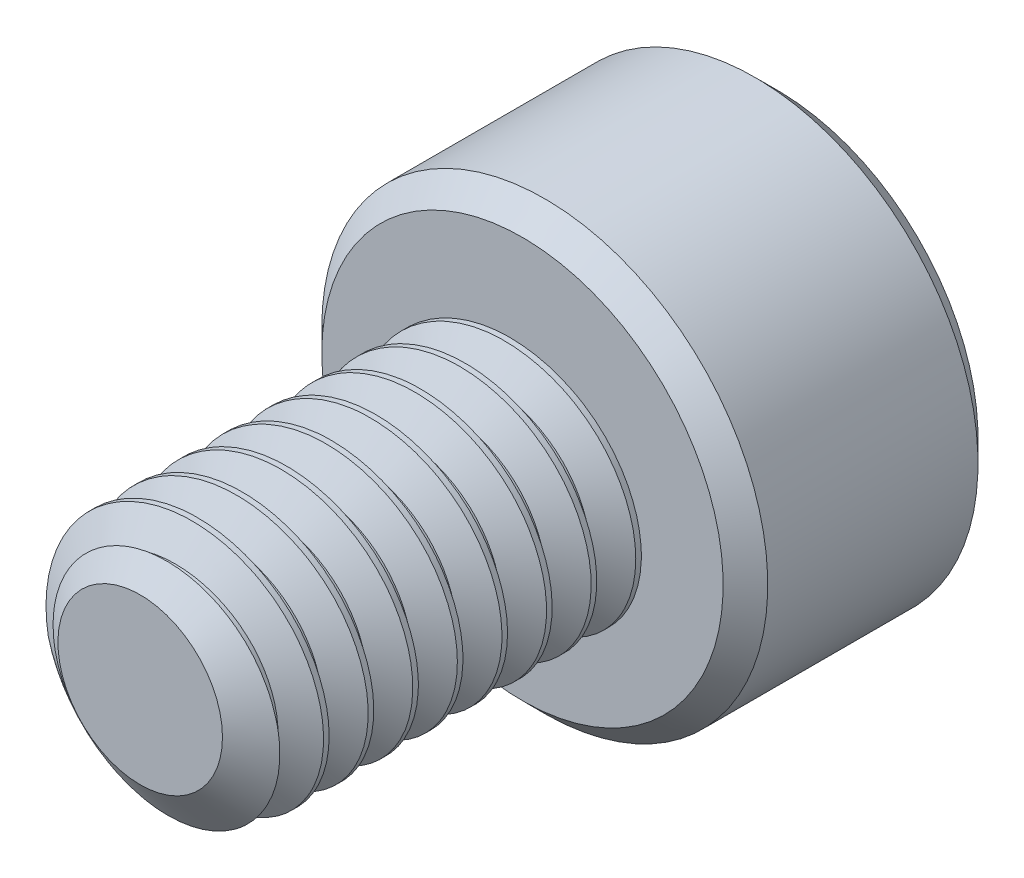
SolidWorks part; units mm, degrees
other "DetailItem1"
material "Stainless Steel 316"
ref_plane "Front Plane" through (0, 0, 0) normal (0, 0, 1) x (1, 0, 0)
ref_plane "Top Plane" through (0, 0, 0) normal (0, 1, 0) x (1, 0, 0)
ref_plane "Right Plane" through (0, 0, 0) normal (1, 0, 0) x (0, 0, -1)
sketch "Sketch1" plane through (0, 0, 0) normal (0, 0, 1) x (1, 0, 0)
  circle A0 centre (0, 0) radius 2
  dimension "OD" = 4
extrude "Extrude1" add sketch "Sketch1" against normal blind 6
sketch "Sketch2" plane through (0, 0, 0) normal (0, 0, 1) x (1, 0, 0)
  circle A0 centre (0, 0) radius 2 construction
  circle A1 centre (0, 0) radius 2
curve "Helix/Spiral1" pitch 0.7 height 6.7 radius 2 centre (0, 0, 0) axis (0, 0, -1) start towards (0, 1, 0) parameters "pitch"=0.7
sketch "Sketch3" plane through (0, 0, 0) normal (1, 0, 0) x (0, 0, -1)
  line L0 (-0.6125, 2) -> (-0.35, 1.5453)
  line L1 (-0.35, 1.5453) -> (-0.2625, 1.5453)
  line L2 (-0.2625, 1.5453) -> (0, 2)
  line L3 (-0.6125, 2) -> (0, 2)
  line L4 (-0.3063, 2) -> (-0.3063, 1.5453) construction
  line L5 (-0.4813, 1.7727) -> (-0.1313, 1.7727) construction
  line L6 (0, 2) -> (0, -2) construction
  dimension "D1" = 0.0875
  dimension "D2" = 0.35
  dimension "D3" = 60
sweep "Cut-Sweep1" cut profiles "Sketch3" path "Helix/Spiral1" align with end faces yes
sketch "Sketch4" plane through (0, 0, 0) normal (1, 0, 0) x (0, 0, -1)
  line L0 (0.4962, 2) -> (0, 1.2913)
  line L1 (0, 1.2913) -> (0, 2)
  line L2 (0.4962, 2) -> (0, 2)
  line L3 (-0.6125, 2) -> (0, 2) construction
  line L4 (0, 0) -> (7.0209, 0) construction
  dimension "D1" = 55
  dimension "D2" = 0.254
revolve "Cut-Revolve1" cut sketch "Sketch4" angle 360 about L4
sketch "Sketch6" plane through (0, 0, -6) normal (0, 0, -1) x (-1, 0, 0)
  circle A0 centre (0, 0) radius 3.5
  dimension "head dia" = 7
extrude "Extrude2" add sketch "Sketch6" along normal blind 4
sketch "Sketch7" plane through (0, 0, -10) normal (0, 0, -1) x (-1, 0, 0)
  line L1 (0, 1.7321) -> (-1.5, 0.866)
  line L2 (-1.5, 0.866) -> (-1.5, -0.866)
  line L3 (-1.5, -0.866) -> (0, -1.7321)
  line L4 (0, -1.7321) -> (1.5, -0.866)
  line L5 (1.5, -0.866) -> (1.5, 0.866)
  line L6 (1.5, 0.866) -> (0, 1.7321)
  circle A0 centre (0, 0) radius 1.5 construction
  dimension "hex dia" = 3
extrude "Cut-Extrude1" cut sketch "Sketch7" against normal blind 2.25
sketch "Sketch8" plane through (0, 0, -10) normal (0, 0, -1) x (-1, 0, 0)
  circle A0 centre (0, 0) radius 1.7321
extrude "Cut-Extrude2" cut sketch "Sketch8" against normal through all draft 45
chamfer "Chamfer1" distance 0.35 angle 45 2 edges at (-3.5, 0, -10) (-3.5, 0, -6)
sketch "Sketch10" plane through (0, 0, -6) normal (0, 0, 1) x (1, 0, 0)
  circle A1 centre (0, 0) radius 2
  circle A2 centre (0, 0) radius 2
  dimension "D1" = 0
ref_plane "Plane1" through (0, 0, 0) normal (0, 0, 1) x (1, 0, 0)
extrude "partial thread" [suppressed] add sketch "Sketch10" along normal up to surface (36 mm away) separate body up to plane "Plane1"
chamfer "Chamfer2" [suppressed] distance 0.08 angle 45
combine bodies "Combine1" [suppressed] operation type add bodies to combine 107 108
sketch "Sketch9" plane through (0, 0, 0) normal (1, 0, 0) x (0, 0, -1)
  line L0 (0, 2) -> (0, -2) construction
  line L1 (1.75, 2) -> (1.75, -2) construction
  dimension "D1" = 1.75
equation "\"D3@Helix/Spiral1\" = \"screw length@Extrude1\"+\"pitch@Helix/Spiral1\""
equation "\"D1@Sketch3\" = \"pitch@Helix/Spiral1\"*.125"
equation "\"D2@Sketch3\" = \"pitch@Helix/Spiral1\"*.5"
equation "\"D1@Cut-Extrude1\" = \"hex dia@Sketch7\"*.75"
equation "\"D1@Chamfer1\" = \"head dia@Sketch6\"*.05"
equation "\"D1@Sketch9\" = \"pitch@Helix/Spiral1\"*2.5"
equation "\"D1@Chamfer2\"=\"OD@Sketch1\"*.02"
